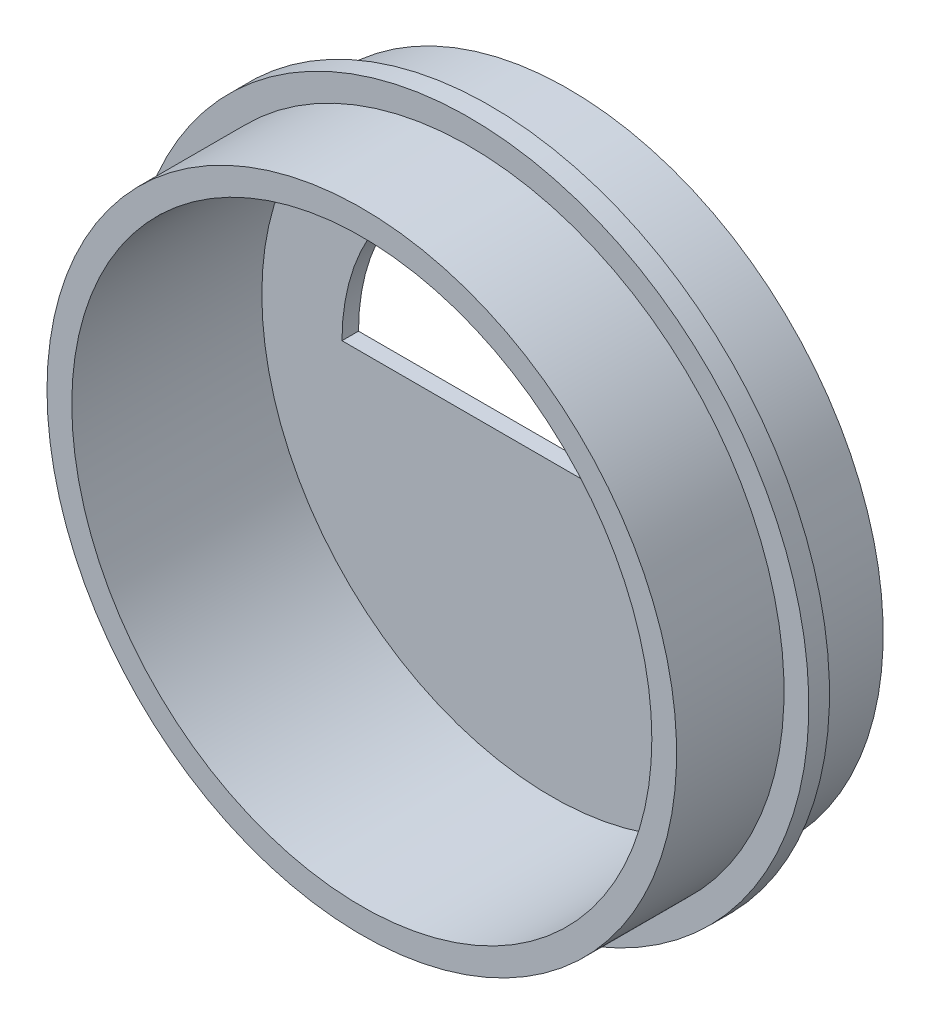
SolidWorks part; units mm, degrees
ref_plane "Front Plane" through (0, 0, 0) normal (0, 0, 1) x (1, 0, 0)
ref_plane "Top Plane" through (0, 0, 0) normal (0, 1, 0) x (1, 0, 0)
ref_plane "Right Plane" through (0, 0, 0) normal (1, 0, 0) x (0, 0, -1)
sketch "Sketch6" plane through (0, 0, 0) normal (1, 0, 0) x (0, 0, -1)
  line L0 (0, 0) -> (-40.103, 0) construction
  line L1 (0, 0) -> (0, 25.4) construction
  line L2 (0, 25.4) -> (-2, 25.4)
  line L3 (-2, 25.4) -> (-2, 35.1)
  line L4 (-2, 35.1) -> (-25, 35.1)
  line L5 (-25, 35.1) -> (-25, 38.1)
  line L6 (-25, 38.1) -> (-12, 38.1)
  line L7 (-12, 38.1) -> (-12, 41.1)
  line L8 (-12, 41.1) -> (-9.5, 41.1)
  line L9 (-9.5, 41.1) -> (-9.5, 38.1)
  line L10 (-9.5, 38.1) -> (0, 38.1)
  line L11 (0, 38.1) -> (0, 25.4)
  dimension "D2" = 25.4
  dimension "D3" = 25
  dimension "D4" = 23
  dimension "D5" = 3
  dimension "D6" = 3
  dimension "D7" = 2.5
  dimension "D8" = 13
  dimension "D9" = 38.1
revolve "Revolve1" add sketch "Sketch6" angle 360 about L0
sketch "Sketch7" plane through (0, 0, 0) normal (0, 0, -1) x (-1, 0, 0)
  line L0 (-25.4, 0) -> (25.4, 0)
  circle A0 centre (0, 0) radius 25.4 construction
  arc A1 (-25.4, 0) -> (25.4, 0) centre (0, 0) ccw
extrude "Boss-Extrude1" add sketch "Sketch7" against normal blind 2
